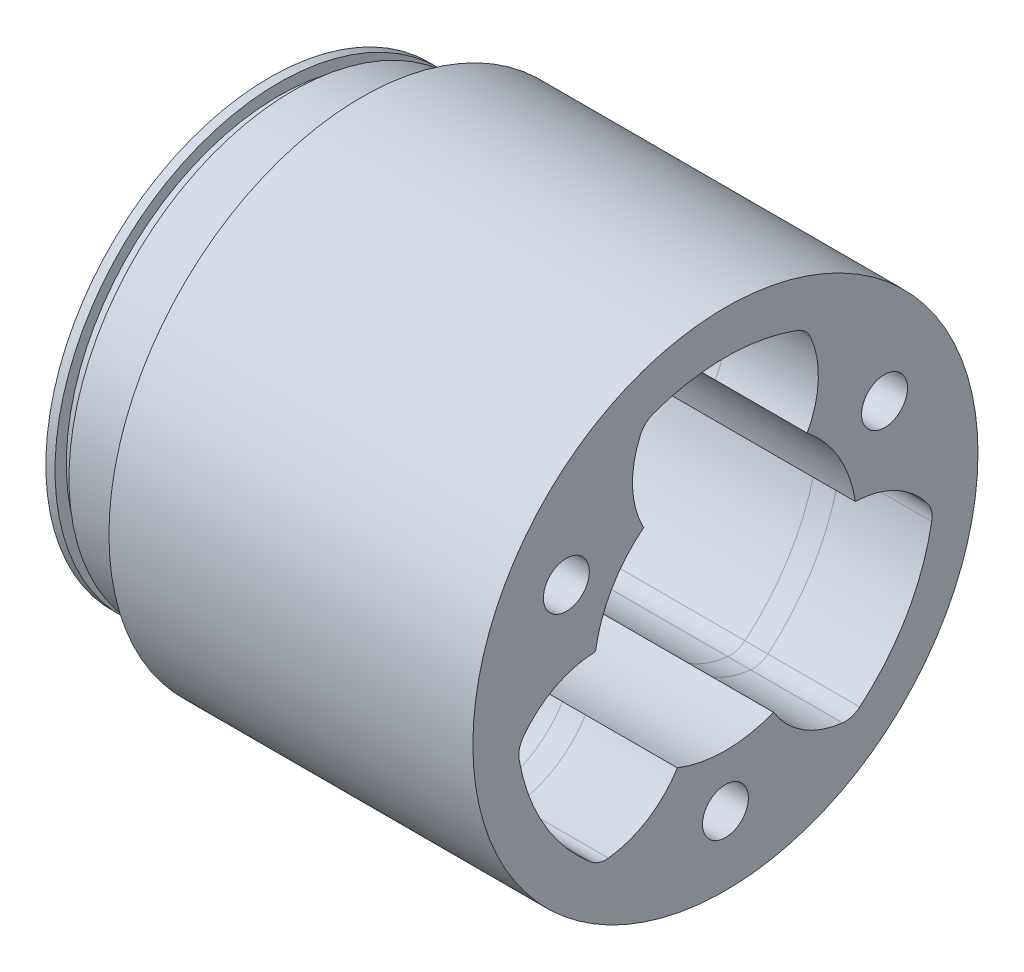
SolidWorks part; units mm, degrees
material "7075-T6 (SN)"
ref_plane "Front Plane" through (0, 0, 0) normal (0, 0, 1) x (1, 0, 0)
ref_plane "Top Plane" through (0, 0, 0) normal (0, 1, 0) x (1, 0, 0)
ref_plane "Right Plane" through (0, 0, 0) normal (1, 0, 0) x (0, 0, -1)
sketch "Sketch2" plane through (0, 0, 0) normal (0, 0, 1) x (1, 0, 0)
  line L0 (0, 0) -> (0, -30.9499)
  line L1 (0, -30.9499) -> (12.7, -30.9499)
  line L2 (12.7, -30.9499) -> (12.7, 0)
  line L3 (12.7, 0) -> (3.2004, 0)
  line L4 (11.9645, -30.9499) -> (0.5681, -30.9499) construction
  line L5 (3.2004, 0) -> (3.2004, -1.5621)
  line L6 (0, 0) -> (1.27, 0)
  line L7 (1.27, 0) -> (1.27, -1.5621)
  line L8 (1.27, -1.5621) -> (3.2004, -1.5621)
  dimension "D4" = 1.9304
  dimension "D5" = 0
  dimension "D6" = 58.7756
  dimension "D1" = 61.8998
  dimension "D2" = 12.7
  dimension "D3" = 1.27
revolve "Revolve1" add sketch "Sketch2" angle 360 about L4
sketch "Bolt Circle Pattern" plane through (12.7, 0, 0) normal (1, 0, 0) x (0, 0, -1)
  circle A3 centre (0, -30.9499) radius 4.1021
  circle A4 centre (0, -30.9499) radius 30.9499 construction
  circle A5 centre (0, -30.9499) radius 9.525 construction
  point P49 (9.525, -30.9499)
  point P51 (0, -40.4749)
  point P53 (-9.525, -30.9499)
  point P57 (0, -21.4249)
  dimension "D1" = 8.2042
  dimension "D2" = 19.05
sketch "Sketch4" plane through (12.7, 0, 0) normal (1, 0, 0) x (0, 0, -1)
  circle A0 centre (0, -30.9499) radius 34.925
  circle A1 centre (0, -30.9499) radius 30.9499 construction
  circle A2 centre (0, -30.9499) radius 18.161
  dimension "D1" = 69.85
  dimension "D2" = 36.322
extrude "Boss-Extrude1" add sketch "Sketch4" along normal blind 72.771
sketch "Sketch5" plane through (0, 0, 0) normal (1, 0, 0) x (0, 0, -1)
  line L0 (0, -10.6299) -> (-17.5976, -41.1099) construction
  line L1 (-17.5976, -41.1099) -> (17.5976, -41.1099) construction
  line L2 (17.5976, -41.1099) -> (0, -10.6299) construction
  line L3 (0, -10.6299) -> (0, -41.1099) construction
  line L4 (-17.5976, -41.1099) -> (8.7988, -25.8699) construction
  line L5 (17.5976, -41.1099) -> (-8.7988, -25.8699) construction
  arc A0 (-11.1418, -4.2233) -> (11.1418, -4.2233) centre (0, -10.6299) ccw
  arc A2 (-28.7168, -34.6641) -> (-17.575, -53.9623) centre (0, -30.9499) ccw
  arc A4 (-17.575, -53.9623) -> (-28.7168, -34.6641) centre (-17.5976, -41.1099) ccw
  arc A5 (28.7168, -34.6641) -> (17.575, -53.9623) centre (17.5976, -41.1099) ccw
  arc A6 (17.575, -53.9623) -> (28.7168, -34.6641) centre (0, -30.9499) ccw
  arc A7 (11.1418, -4.2233) -> (-11.1418, -4.2233) centre (0, -30.9499) ccw
  dimension "D2" = 12.8524
  dimension "D6" = 12.8524
  dimension "D5" = 12.8524
  dimension "D9" = 28.956
  dimension "D1" = 20.32
  dimension "D3" = 20.32
  dimension "D4" = 20.32
  dimension "D7" = 35.1953
  dimension "D8" = 35.1953
extrude "Cut-Extrude2" cut sketch "Sketch5" along normal up to next from offset 21.75
fillet "Tripod walls" radius 3.175 6 edges at (53.6105, -53.9623, 17.575) (53.6105, -53.9623, -17.575) (53.6105, -34.6641, 28.7168) (53.6105, -34.6641, -28.7168) (53.6105, -4.2233, 11.1418) (53.6105, -4.2233, -11.1418)
fillet "Tripod Face" [suppressed] radius 3.175
fillet "Bolt Hole Face" radius 3.175 1 edges at (12.7, -30.9499, -18.161)
ref_plane "Plane1" through (60.071, 0, 0) normal (1, 0, 0) x (0, 0, -1)
ref_plane "Plane2" through (66.421, 0, 0) normal (1, 0, 0) x (0, 0, -1)
split line "Split Line1" [suppressed]
sketch "Sketch12" plane through (85.471, 0, 0) normal (1, 0, 0) x (0, 0, -1)
  line L0 (-21.997, -18.2499) -> (21.997, -18.2499) construction
  line L1 (21.997, -18.2499) -> (0, -56.3499) construction
  line L2 (0, -56.3499) -> (-21.997, -18.2499) construction
  circle A0 centre (0, -30.9499) radius 25.4 construction
  circle A4 centre (-21.997, -18.2499) radius 3.175
  circle A9 centre (21.997, -18.2499) radius 3.175
  circle A12 centre (0, -56.3499) radius 3.175
  dimension "D2" = 6.35
  dimension "D1" = 50.8
extrude "Cut-Extrude3" cut sketch "Sketch12" against normal blind 63.5
sketch "Sketch13" plane through (85.471, 0, 0) normal (1, 0, 0) x (0, 0, -1)
  circle A1 centre (0, -30.9499) radius 34.925
  circle A2 centre (0, -30.9499) radius 34.925
  dimension "D1" = 0
extrude "Cut-Extrude4" cut sketch "Sketch13" against normal offset from surface (22.446 mm away) 41.275 up to face at (21.75, -42.5964, -20.1724)
fillet "Fillet6" [suppressed] radius 2.54
ref_plane "Plane5" through (24.925, 0, 0) normal (1, 0, 0) x (0, 0, -1)
split line "Split Line4"
sketch "Sketch14" [suppressed] plane through (63.025, 0, 0) normal (1, 0, 0) x (0, 0, -1)
  circle A0 centre (0, -30.5867) radius 18.161
  circle A1 centre (0, -30.5867) radius 18.161 construction
ref_plane "Plane3" through (47.15, 0, 0) normal (1, 0, 0) x (0, 0, -1)
split line "Split Line2"
ref_plane "Plane4" through (50.325, 0, 0) normal (1, 0, 0) x (0, 0, -1)
split line "Split Line3"
sketch "Sketch16" plane through (0, 0, 0) normal (-1, 0, 0) x (0, 0, 1)
  circle A0 centre (0, -30.9499) radius 22.86
  circle A1 centre (0, -30.9499) radius 30.9499 construction
  dimension "D1" = 45.72
extrude "Compensating Spacing" add sketch "Sketch16" along normal blind 1.016
hole_wizard "1/4 (0.2500) Dowel Hole1" positions "Bolt Circle Pattern" profile "Sketch15" hole size "1/4" standard "ANSI Inch" end condition through all
sketch "Sketch15" plane through (12.7, -21.4249, 0) normal (0, 1, 0) x (0, 0, -1)
  line L0 (0, 0) -> (0, 13.716)
  line L1 (0, 13.716) -> (3.175, 13.716)
  line L2 (3.175, 13.716) -> (3.175, 0)
  line L5 (3.175, 0) -> (0, 0)
  line L11 (0, -6.35) -> (0, 107.95) construction
  dimension "Thru Hole Dia." = 6.35
  dimension "Thru Hole Depth" = 13.716
extrude "5/16 Clearnce" cut sketch "Bolt Circle Pattern<2>" against normal up to surface (13.716 mm away) up to face at (-1.016, -30.9499, 6.35)
sketch "Bolt Circle Pattern<2>" plane through (12.7, 0, 0) normal (1, 0, 0) x (0, 0, -1) same geometry as "Bolt Circle Pattern"
equation "\"D9@Sketch5\"=2.28/2"
equation "\"D8@Sketch5\"=\"D7@Sketch5\""
equation "\"Drill_Hole\"=0.25"
equation "\"D2@Sketch12\"=\"Drill_Hole\""
